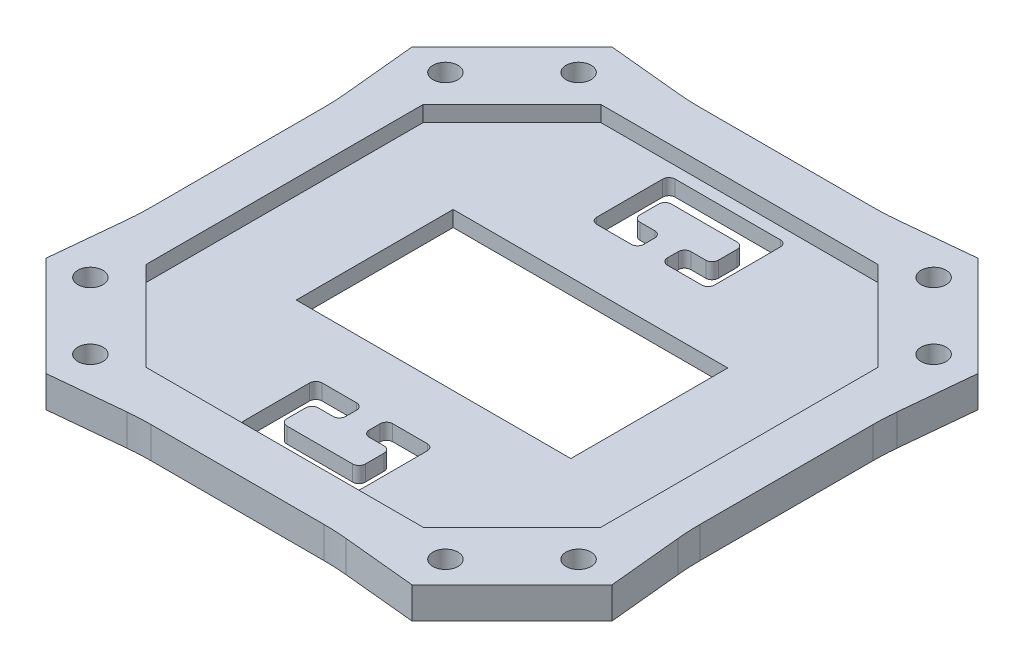
SolidWorks part; units mm, degrees
ref_plane "Front Plane" through (0, 0, 0) normal (0, 0, 1) x (1, 0, 0)
ref_plane "Top Plane" through (0, 0, 0) normal (0, 1, 0) x (1, 0, 0)
ref_plane "Right Plane" through (0, 0, 0) normal (1, 0, 0) x (0, 0, -1)
sketch "Sketch1" plane through (0, 0, 0) normal (0, 1, 0) x (1, 0, 0)
  line L0 (0, 0) -> (84.8528, 84.8528) construction
  line L1 (35, -35) -> (-35, -35) construction
  line L2 (35, -35) -> (35, 35) construction
  line L3 (35, 35) -> (-35, 35) construction
  line L4 (-35, -35) -> (-35, 35) construction
  line L5 (35, -35) -> (-35, 35) construction
  line L6 (35, 35) -> (-35, -35) construction
  line L7 (0, 35) -> (0, -35) construction
  line L8 (-12.5, 35) -> (12.5, 35)
  line L9 (35, 12.5) -> (35, -12.5)
  line L10 (12.5, -35) -> (-12.5, -35)
  line L11 (-35, -12.5) -> (-35, 12.5)
  line L12 (20.5061, 33.234) -> (33.234, 20.5061) construction
  line L13 (23.3345, 36.0624) -> (36.0624, 23.3345)
  line L14 (12.5, 35) -> (23.3345, 36.0624)
  line L15 (35, 12.5) -> (36.0624, 23.3345)
  line L16 (36.0624, -23.3345) -> (23.3345, -36.0624)
  line L17 (35, -12.5) -> (36.0624, -23.3345)
  line L18 (12.5, -35) -> (23.3345, -36.0624)
  line L19 (-23.3345, -36.0624) -> (-36.0624, -23.3345)
  line L20 (-12.5, -35) -> (-23.3345, -36.0624)
  line L21 (-35, -12.5) -> (-36.0624, -23.3345)
  line L22 (-36.0624, 23.3345) -> (-23.3345, 36.0624)
  line L23 (-35, 12.5) -> (-36.0624, 23.3345)
  line L24 (-12.5, 35) -> (-23.3345, 36.0624)
  circle A0 centre (22.6274, 31.1127) radius 1.6
  circle A1 centre (31.1127, 22.6274) radius 1.6
  circle A2 centre (22.6274, -31.1127) radius 1.6
  circle A3 centre (31.1127, -22.6274) radius 1.6
  circle A4 centre (-31.1127, -22.6274) radius 1.6
  circle A5 centre (-22.6274, -31.1127) radius 1.6
  circle A6 centre (-22.6274, 31.1127) radius 1.6
  circle A7 centre (-31.1127, 22.6274) radius 1.6
  point P0 (0, 0)
  point P27 (26.8701, 26.8701)
  point P30 (0, 0)
  point P39 (0, 0)
  point P48 (0, 0)
  dimension "D7" = 3.2
  dimension "D8" = 6
  dimension "D13" = 4
  dimension "D1" = 70
  dimension "D2" = 70
  dimension "D3" = 120
  dimension "D4" = 25
  dimension "D5" = 12.5
  dimension "D9" = 82
  dimension "D10" = 4
  dimension "D11" = 18
  dimension "D12" = 6
  dimension "D6" = 4
extrude "Boss-Extrude1" add sketch "Sketch1" along normal blind 4
sketch "Sketch2" plane through (0, 4, 0) normal (0, 1, 0) x (1, 0, 0)
  line L0 (0, 34.2898) -> (0, 0) construction
  line L1 (0, 0) -> (-35, 0) construction
  line L2 (-35, 12.5) -> (-35, -12.5) construction
  line L3 (-17.669, 29) -> (17.669, 29)
  line L4 (17.669, 29) -> (29, 17.669)
  line L5 (29, 17.669) -> (29, -17.669)
  line L6 (29, -17.669) -> (17.669, -29)
  line L7 (17.669, -29) -> (-17.669, -29)
  line L8 (-17.669, -29) -> (-29, -17.669)
  line L9 (-29, -17.669) -> (-29, 17.669)
  line L10 (-29, 17.669) -> (-17.669, 29)
  line L11 (-12.5, -35) -> (12.5, -35) construction
  line L12 (-36.0624, -23.3345) -> (-23.3345, -36.0624) construction
  line L13 (36.0624, 23.3345) -> (23.3345, 36.0624) construction
  line L14 (23.3345, -36.0624) -> (36.0624, -23.3345) construction
  dimension "D1" = 6
  dimension "D2" = 6
  dimension "D3" = 9
  dimension "D4" = 9
  dimension "D5" = 9
extrude "Cut-Extrude1" cut sketch "Sketch2" against normal blind 2 contours L10 L3 L4 L5 L6 L7 L8 L9
sketch "Sketch3" plane through (0, 2, 0) normal (0, 1, 0) x (1, 0, 0)
  line L0 (0, 29) -> (0, 0) construction
  line L1 (-17.669, 29) -> (17.669, 29) construction
  line L2 (0, 0) -> (-29, 0) construction
  line L3 (-29, -17.669) -> (-29, 17.669) construction
  line L4 (-24.0792, 13.5676) -> (-16.0792, 6.8995)
  line L5 (-15, 4.5951) -> (-15, -4.5951)
  line L6 (-16.0792, -6.8995) -> (-24.0792, -13.5676)
  line L7 (-29, -11.2631) -> (-29, 11.2631)
  line L8 (-11.2631, 29) -> (11.2631, 29)
  line L9 (-6.8995, 16.0792) -> (-13.5676, 24.0792)
  line L10 (4.5951, 15) -> (-4.5951, 15)
  line L11 (13.5676, 24.0792) -> (6.8995, 16.0792)
  line L12 (29, 11.2631) -> (29, -11.2631)
  line L13 (16.0792, 6.8995) -> (24.0792, 13.5676)
  line L14 (15, -4.5951) -> (15, 4.5951)
  line L15 (24.0792, -13.5676) -> (16.0792, -6.8995)
  line L16 (11.2631, -29) -> (-11.2631, -29)
  line L17 (6.8995, -16.0792) -> (13.5676, -24.0792)
  line L18 (-4.5951, -15) -> (4.5951, -15)
  line L19 (-13.5676, -24.0792) -> (-6.8995, -16.0792)
  arc A0 (-16.0792, 6.8995) -> (-15, 4.5951) centre (-18, 4.5951) cw
  arc A1 (-15, -4.5951) -> (-16.0792, -6.8995) centre (-18, -4.5951) cw
  arc A2 (-24.0792, -13.5676) -> (-29, -11.2631) centre (-26, -11.2631) cw
  arc A3 (-24.0792, 13.5676) -> (-29, 11.2631) centre (-26, 11.2631) ccw
  arc A4 (-13.5676, 24.0792) -> (-11.2631, 29) centre (-11.2631, 26) cw
  arc A5 (-4.5951, 15) -> (-6.8995, 16.0792) centre (-4.5951, 18) cw
  arc A6 (6.8995, 16.0792) -> (4.5951, 15) centre (4.5951, 18) cw
  arc A7 (13.5676, 24.0792) -> (11.2631, 29) centre (11.2631, 26) ccw
  arc A8 (24.0792, 13.5676) -> (29, 11.2631) centre (26, 11.2631) cw
  arc A9 (15, 4.5951) -> (16.0792, 6.8995) centre (18, 4.5951) cw
  arc A10 (16.0792, -6.8995) -> (15, -4.5951) centre (18, -4.5951) cw
  arc A11 (24.0792, -13.5676) -> (29, -11.2631) centre (26, -11.2631) ccw
  arc A12 (13.5676, -24.0792) -> (11.2631, -29) centre (11.2631, -26) cw
  arc A13 (4.5951, -15) -> (6.8995, -16.0792) centre (4.5951, -18) cw
  arc A14 (-6.8995, -16.0792) -> (-4.5951, -15) centre (-4.5951, -18) cw
  arc A15 (-13.5676, -24.0792) -> (-11.2631, -29) centre (-11.2631, -26) ccw
  point P16 (-15, 0)
  point P19 (-15, 6)
  point P22 (-15, -6)
  point P25 (-29, -17.669)
  point P28 (-29, 17.669)
  dimension "D3" = 3
  dimension "D1" = 15
  dimension "D2" = 12
  dimension "D4" = 4
extrude "Cut-Extrude2" [suppressed] cut sketch "Sketch3" against normal blind 1.5
sketch "Sketch4" plane through (0, 2, 0) normal (0, 1, 0) x (1, 0, 0)
  line L1 (0, 0) -> (15.25, 0) construction
  line L2 (0, 0) -> (0, 15.25) construction
  line L3 (0, 15.25) -> (15.25, 15.25) construction
  line L4 (15.25, 0) -> (15.25, 15.25) construction
  circle A0 centre (15.25, 15.25) radius 1.5
  dimension "D2" = 3
  dimension "D1" = 15.25
extrude "Cut-Extrude4" [suppressed] cut sketch "Sketch4" against normal through all
sketch "Sketch5" [suppressed] plane through (0, 2, 0) normal (0, 1, 0) x (1, 0, 0)
  circle A0 centre (15.25, 15.25) radius 4
  circle A1 centre (15.25, 15.25) radius 1.5 construction
  circle A2 centre (15.25, 15.25) radius 1.5
  dimension "D1" = 8
extrude "Boss-Extrude2" [suppressed] add sketch "Sketch5" along normal blind 1.5
ref_axis "Axis1" [suppressed] through (0, -0.2, 0) along (0, 1, 0)
pattern_circular "CirPattern1" [suppressed] count 4 over 360 about axis through (0, -0.2, 0) along (0, 1, 0) of bodies 108
fillet "Fillet1" [suppressed] radius 2
fillet "Fillet2" radius 30 8 edges at (12.5, 2, -35) (-12.5, 2, -35) (-35, 2, -12.5) (-35, 2, 12.5) (35, 2, -12.5) (35, 2, 12.5) (12.5, 2, 35) (-12.5, 2, 35)
sketch "Sketch6" plane through (0, 2, 0) normal (0, 1, 0) x (1, 0, 0)
  line L0 (0, 27.5876) -> (0, 0) construction
  line L1 (0, 0) -> (-24.3451, 0) construction
  line L2 (-1.5, 19.7) -> (-1.5, 18.3)
  line L3 (6.7, 17.5) -> (2.3, 17.5)
  line L4 (7.5, 18.3) -> (7.5, 26.7)
  line L5 (6.7, 27.5) -> (-6.7, 27.5)
  line L6 (-7.5, 18.3) -> (-7.5, 26.7)
  line L7 (7.5, 17.5) -> (-7.5, 27.5) construction
  line L8 (7.5, 27.5) -> (-7.5, 17.5) construction
  line L9 (4.2, 24.5) -> (-4.2, 24.5)
  line L10 (5, 23.7) -> (5, 21.3)
  line L11 (4.2, 20.5) -> (2.3, 20.5)
  line L12 (-5, 23.7) -> (-5, 21.3)
  line L13 (5, 24.5) -> (-5, 20.5) construction
  line L14 (5, 20.5) -> (-5, 24.5) construction
  line L15 (1.5, 19.7) -> (1.5, 18.3)
  line L16 (-2.3, 20.5) -> (-4.2, 20.5)
  line L17 (-2.3, 17.5) -> (-6.7, 17.5)
  line L18 (5, -20.5) -> (-5, -24.5) construction
  line L19 (5, -24.5) -> (-5, -20.5) construction
  line L20 (7.5, -27.5) -> (-7.5, -17.5) construction
  line L21 (7.5, -17.5) -> (-7.5, -27.5) construction
  line L22 (-2.3, -17.5) -> (-6.7, -17.5)
  line L23 (-2.3, -20.5) -> (-4.2, -20.5)
  line L24 (1.5, -19.7) -> (1.5, -18.3)
  line L25 (-5, -23.7) -> (-5, -21.3)
  line L26 (4.2, -20.5) -> (2.3, -20.5)
  line L27 (5, -23.7) -> (5, -21.3)
  line L28 (4.2, -24.5) -> (-4.2, -24.5)
  line L29 (-7.5, -18.3) -> (-7.5, -26.7)
  line L30 (6.7, -27.5) -> (-6.7, -27.5)
  line L31 (7.5, -18.3) -> (7.5, -26.7)
  line L32 (6.7, -17.5) -> (2.3, -17.5)
  line L33 (-1.5, -19.7) -> (-1.5, -18.3)
  arc A0 (1.5, 18.3) -> (2.3, 17.5) centre (2.3, 18.3) ccw
  arc A1 (1.5, 19.7) -> (2.3, 20.5) centre (2.3, 19.7) cw
  arc A2 (-1.5, 18.3) -> (-2.3, 17.5) centre (-2.3, 18.3) cw
  arc A3 (-1.5, 19.7) -> (-2.3, 20.5) centre (-2.3, 19.7) ccw
  arc A4 (-4.2, 24.5) -> (-5, 23.7) centre (-4.2, 23.7) ccw
  arc A5 (5, 21.3) -> (4.2, 20.5) centre (4.2, 21.3) cw
  arc A6 (4.2, 24.5) -> (5, 23.7) centre (4.2, 23.7) cw
  arc A7 (-4.2, 20.5) -> (-5, 21.3) centre (-4.2, 21.3) cw
  arc A8 (-6.7, 17.5) -> (-7.5, 18.3) centre (-6.7, 18.3) cw
  arc A9 (7.5, 26.7) -> (6.7, 27.5) centre (6.7, 26.7) ccw
  arc A10 (6.7, 17.5) -> (7.5, 18.3) centre (6.7, 18.3) ccw
  arc A11 (-6.7, 27.5) -> (-7.5, 26.7) centre (-6.7, 26.7) ccw
  arc A12 (-6.7, -27.5) -> (-7.5, -26.7) centre (-6.7, -26.7) cw
  arc A13 (6.7, -17.5) -> (7.5, -18.3) centre (6.7, -18.3) cw
  arc A14 (7.5, -26.7) -> (6.7, -27.5) centre (6.7, -26.7) cw
  arc A15 (-6.7, -17.5) -> (-7.5, -18.3) centre (-6.7, -18.3) ccw
  arc A16 (-4.2, -20.5) -> (-5, -21.3) centre (-4.2, -21.3) ccw
  arc A17 (4.2, -24.5) -> (5, -23.7) centre (4.2, -23.7) ccw
  arc A18 (5, -21.3) -> (4.2, -20.5) centre (4.2, -21.3) ccw
  arc A19 (-4.2, -24.5) -> (-5, -23.7) centre (-4.2, -23.7) cw
  arc A20 (-1.5, -19.7) -> (-2.3, -20.5) centre (-2.3, -19.7) cw
  arc A21 (-1.5, -18.3) -> (-2.3, -17.5) centre (-2.3, -18.3) ccw
  arc A22 (1.5, -19.7) -> (2.3, -20.5) centre (2.3, -19.7) ccw
  arc A23 (1.5, -18.3) -> (2.3, -17.5) centre (2.3, -18.3) cw
  point P4 (0, 22.5)
  point P9 (0, 22.5)
  point P20 (1.5, 17.5)
  point P23 (1.5, 20.5)
  point P26 (-1.5, 17.5)
  point P29 (-1.5, 20.5)
  point P98 (-1.5, -20.5)
  point P99 (-1.5, -17.5)
  point P100 (1.5, -20.5)
  point P101 (1.5, -17.5)
  point P102 (0, -22.5)
  dimension "D7" = 0.8
  dimension "D1" = 17.5
  dimension "D2" = 15
  dimension "D3" = 10
  dimension "D4" = 2.5
  dimension "D5" = 3
  dimension "D6" = 6
extrude "Cut-Extrude5" cut sketch "Sketch6" against normal through all
sketch "Sketch7" plane through (0, 2, 0) normal (0, 1, 0) x (1, 0, 0)
  line L1 (17.5, -10) -> (-17.5, -10)
  line L2 (17.5, -10) -> (17.5, 10)
  line L3 (17.5, 10) -> (-17.5, 10)
  line L4 (-17.5, -10) -> (-17.5, 10)
  line L5 (17.5, -10) -> (-17.5, 10) construction
  line L6 (17.5, 10) -> (-17.5, -10) construction
  point P0 (0, 0)
  dimension "D1" = 35
  dimension "D2" = 20
extrude "Cut-Extrude6" cut sketch "Sketch7" against normal through all
equation "\"360degdeg\"=360"
